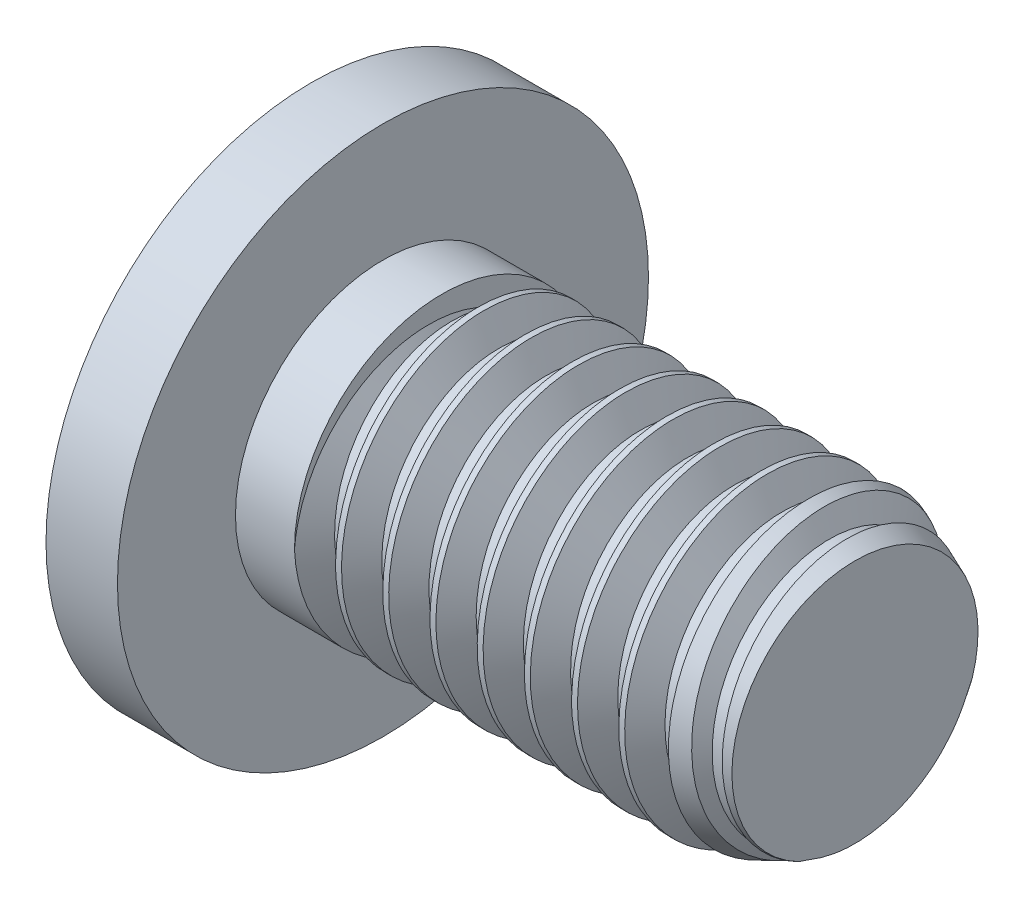
SolidWorks part; units mm, degrees
material "PEEK-15"
ref_plane "Front Plane" through (0, 0, 0) normal (0, 0, 1) x (1, 0, 0)
ref_plane "Top Plane" through (0, 0, 0) normal (0, 1, 0) x (1, 0, 0)
ref_plane "Right Plane" through (0, 0, 0) normal (1, 0, 0) x (0, 0, -1)
sketch "Sketch1" plane through (0, 0, 0) normal (0, 0, 1) x (1, 0, 0)
  line L0 (0, 4.021) -> (0, -3.3403) construction
  line L1 (8, 4.021) -> (8, -3.3403) construction
  line L2 (0, 0) -> (8, 0) construction
  dimension "LENGTH" = 8
sketch "Sketch2" plane through (0, 0, 0) normal (1, 0, 0) x (0, 0, -1)
  circle A0 centre (0, 0) radius 2.5
  dimension "D1" = 5
extrude "Boss-Extrude1" add sketch "Sketch2" along normal up to vertex (8 mm away) up to point (8, 0, 0)
chamfer "Chamfer1" distance 1 angle 22.5 1 edges at (8, 0, -2.5) first distance on face at (8, 0, -2.5)
thread "Thread1" pitch 0.8 method cut profile "Thread Profile1" start angle 0, offset 1, length 0, pitch 0.8, diameter 5
ref_plane "Plane1" through (-1, 0, -2.5) normal (0, -1, 0) x (0, 0, -1)
sketch "Thread Profile1" plane through (-1, 0, -2.5) normal (0, -1, 0) x (0, 0, -1)
  line L0 (0, 0) -> (0, 0.8) construction
  line L11 (0, 0) -> (0, 0.7)
  line L12 (0, 0.7) -> (-0.433, 0.45)
  line L13 (-0.433, 0.45) -> (-0.433, 0.25)
  line L15 (-0.433, 0.25) -> (0, 0)
  line L17 (-0.433, 0.35) -> (0, 0.35) construction
  point P2 (0, 0)
  dimension "Pitch" = 0.8
  dimension "Profile_Angle" = 60
  dimension "Profile_Land" = 0.2
  dimension "Profile_Height" = 0.433
sketch "Sketch5" plane through (0, 0, 0) normal (-1, 0, 0) x (0, 0, 1)
  circle A0 centre (0, 0) radius 4.5
  dimension "D1" = 9
extrude "Boss-Extrude2" add sketch "Sketch5" along normal blind 1.5
sketch "Sketch6" plane through (-1.5, 0, 0) normal (-1, 0, 0) x (0, 0, 1)
  line L1 (-2, -1.1547) -> (0, -2.3094)
  line L2 (0, -2.3094) -> (2, -1.1547)
  line L3 (2, -1.1547) -> (2, 1.1547)
  line L4 (2, 1.1547) -> (0, 2.3094)
  line L5 (0, 2.3094) -> (-2, 1.1547)
  line L6 (-2, 1.1547) -> (-2, -1.1547)
  circle A0 centre (0, 0) radius 2 construction
  dimension "D1" = 4
extrude "Cut-Extrude1" cut sketch "Sketch6" against normal blind 2.5
chamfer "Chamfer2" distance 0.5 angle 30 1 edges at (-1.5, 0, 4.5) first distance on face at (-1.5, 0, 0)
sketch "Croquis1" plane through (0, 0, 0) normal (1, 0, 0) x (0, 0, -1)
  circle A0 centre (0, 0) radius 2.5
extrude "Saliente-Extruir1" add sketch "Croquis1" along normal blind 1
